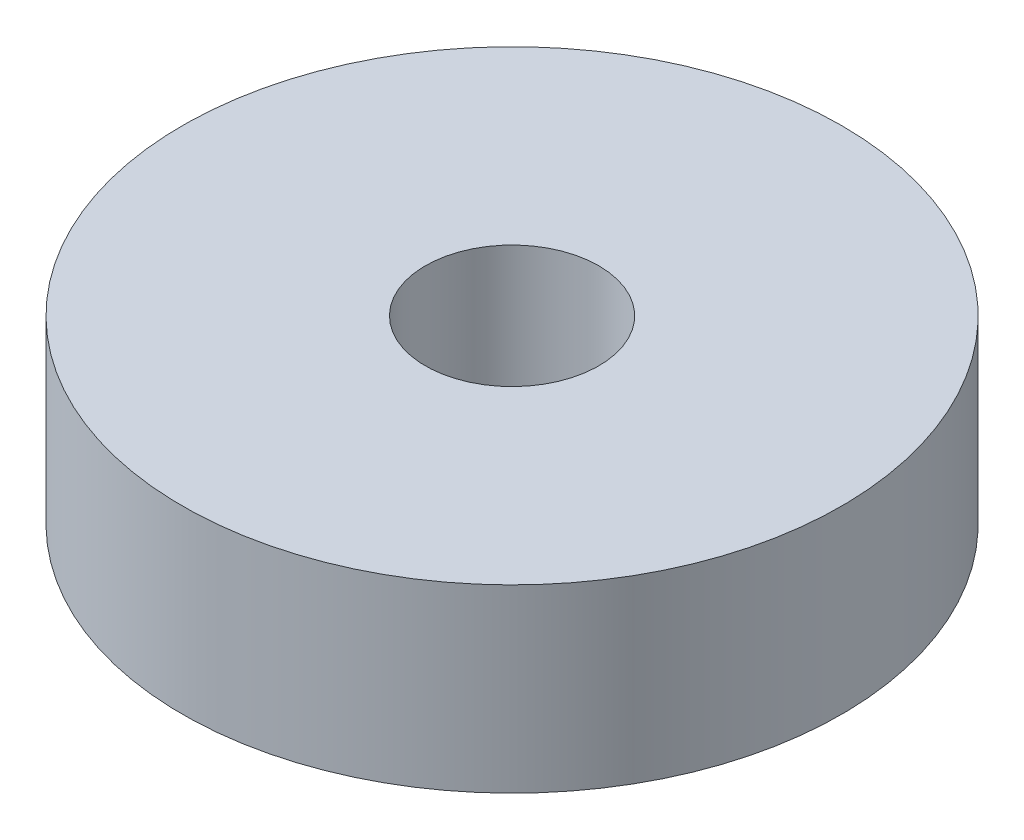
SolidWorks part; units mm, degrees
ref_plane "Front Plane" through (0, 0, 0) normal (0, 0, 1) x (1, 0, 0)
ref_plane "Top Plane" through (0, 0, 0) normal (0, 1, 0) x (1, 0, 0)
ref_plane "Right Plane" through (0, 0, 0) normal (1, 0, 0) x (0, 0, -1)
sketch "Sketch1" plane through (0, 0, 0) normal (0, 1, 0) x (1, 0, 0)
  circle A0 centre (0, 0) radius 47.5
  dimension "FLANGE_OD" = 95
extrude "Boss-Extrude1" add sketch "Sketch1" along normal blind 26
sketch "Sketch2" plane through (0, 0, 0) normal (0, 1, 0) x (1, 0, 0)
  circle A0 centre (0, 0) radius 12.5
  dimension "BORE_D" = 25
extrude "Cut-Extrude1" cut sketch "Sketch2" along normal through all
sketch "Sketch3" plane through (0, 26, 0) normal (0, 1, 0) x (1, 0, 0)
  circle A0 centre (0, 0) radius 8.9518 construction
  circle A1 centre (-8.9518, 0) radius 3.4479
  dimension "BOLT_D" = 6.8958
  dimension "BOLT_PCD" = 17.9035
extrude "Cut-Extrude2" cut sketch "Sketch3" against normal blind 22.8406 rebuild error yes
pattern_circular "CirPattern1" count 4 over 360 rebuild error yes
